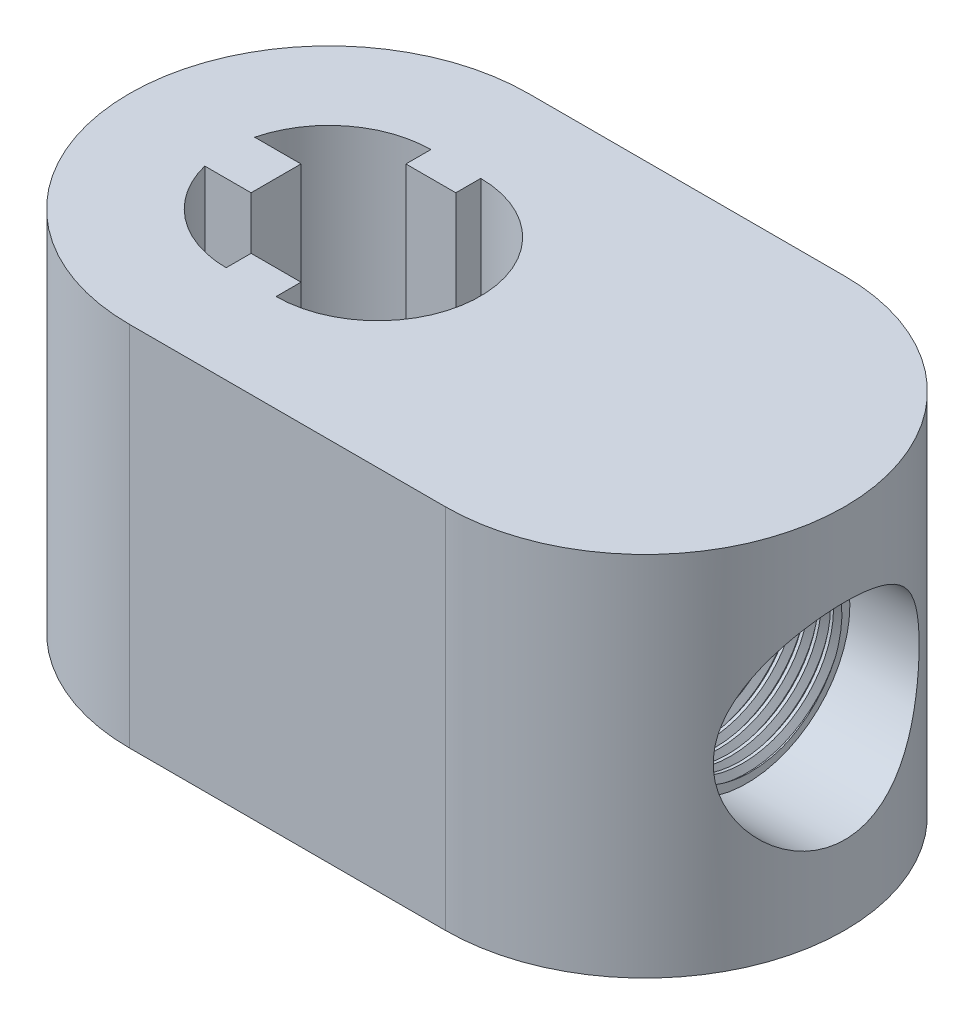
SolidWorks part; units mm, degrees
ref_plane "Front Plane" through (0, 0, 0) normal (0, 0, 1) x (1, 0, 0)
ref_plane "Top Plane" through (0, 0, 0) normal (0, 1, 0) x (1, 0, 0)
ref_plane "Right Plane" through (0, 0, 0) normal (1, 0, 0) x (0, 0, -1)
sketch "Sketch1" plane through (0, 0, 0) normal (0, 1, 0) x (1, 0, 0)
  line L0 (0, 8.165) -> (12.92, 8.165)
  line L1 (0, -8.165) -> (12.92, -8.165)
  circle A0 centre (0, 0) radius 8.165 construction
  arc A1 (12.92, 8.165) -> (12.92, -8.165) centre (12.92, 0) cw
  arc A2 (0, 8.165) -> (0, -8.165) centre (0, 0) ccw
  dimension "D1" = 12.92
  dimension "D2" = 16.33
extrude "Boss-Extrude1" add sketch "Sketch1" along normal blind 15
sketch "Sketch2" plane through (0, 15, 0) normal (0, 1, 0) x (1, 0, 0)
  line L0 (0, 0) -> (2, 0) construction
  line L1 (0, 4.185) -> (2, 4.185)
  line L2 (0, -4.185) -> (2, -4.185)
  arc A1 (0, 4.185) -> (0, -4.185) centre (0, 0) ccw
  arc A2 (2, -4.185) -> (2, 4.185) centre (2, 0) ccw
  point P3 (1, 0)
  dimension "D1" = 8.37
extrude "Cut-Extrude1" cut sketch "Sketch2" against normal blind 11.25
ref_plane "Plane1" through (21.085, 0, 0) normal (1, 0, 0) x (0, 0, -1)
sketch "Sketch3" plane through (21.085, 0, 0) normal (1, 0, 0) x (0, 0, -1)
  line L1 (-8.165, 3.75) -> (8.165, 3.75) construction
  line L2 (-8.165, 15) -> (-8.165, 0) construction
  line L3 (8.165, 15) -> (8.165, 0) construction
  line L4 (8.165, 15) -> (-8.165, 15) construction
  circle A0 centre (0, 7.415) radius 3.665
  dimension "D1" = 7.33
  dimension "D2" = 11.25
extrude "Cut-Extrude2" cut sketch "Sketch3" against normal blind 22
sketch "Sketch4" plane through (21.085, 0, 0) normal (1, 0, 0) x (0, 0, -1)
  circle A0 centre (0, 7.415) radius 4.21
  circle A1 centre (0, 7.415) radius 3.665 construction
  dimension "D1" = 8.42
extrude "Cut-Extrude3" cut sketch "Sketch4" against normal blind 4
thread "Thread1" pitch 0.5 method cut profile "Thread Profile1" start angle 0, offset 4, length 10, pitch 0.5, diameter 7.33
ref_plane "Plane2" through (21.085, 7.415, 3.665) normal (0, -1, 0) x (0, 0, 1)
sketch "Thread Profile1" plane through (21.085, 7.415, 3.665) normal (0, -1, 0) x (0, 0, 1)
  line L0 (0, 0) -> (0, 0.5) construction
  line L1 (0, 0) -> (0.2706, 0.1562)
  line L2 (0.2706, 0.1562) -> (0.2706, 0.2187)
  line L3 (0.2706, 0.2187) -> (0, 0.375)
  line L4 (0.2706, 0.1875) -> (0, 0.1875) construction
  line L11 (0, 0) -> (0, 0.375)
  point P2 (0, 0)
  dimension "Pitch" = 0.5
  dimension "Profile_Angle" = 60
  dimension "Profile_Land" = 0.0625
  dimension "Profile_Height" = 0.2706
sketch "Sketch7" plane through (0, 15, 0) normal (0, 1, 0) x (1, 0, 0)
  line L0 (2, 4.185) -> (0, 4.185) construction
  line L1 (-4.185, 1.02) -> (-2.165, 1.02)
  line L2 (-4.185, 1.02) -> (-4.185, -1.02)
  line L3 (-4.185, -1.02) -> (-2.165, -1.02)
  line L4 (-2.165, 1.02) -> (-2.165, -1.02)
  line L5 (-4.185, 1.02) -> (-2.165, -1.02) construction
  line L6 (-4.185, -1.02) -> (-2.165, 1.02) construction
  line L7 (-0.02, 5.205) -> (2.02, 5.205)
  line L8 (-0.02, 5.205) -> (-0.02, 3.165)
  line L9 (-0.02, 3.165) -> (2.02, 3.165)
  line L10 (2.02, 5.205) -> (2.02, 3.165)
  line L11 (-0.02, 5.205) -> (2.02, 3.165) construction
  line L12 (-0.02, 3.165) -> (2.02, 5.205) construction
  line L13 (-0.02, -3.165) -> (2.02, -3.165)
  line L14 (-0.02, -3.165) -> (-0.02, -5.205)
  line L15 (-0.02, -5.205) -> (2.02, -5.205)
  line L16 (2.02, -3.165) -> (2.02, -5.205)
  line L17 (-0.02, -3.165) -> (2.02, -5.205) construction
  line L18 (-0.02, -5.205) -> (2.02, -3.165) construction
  line L19 (0, -4.185) -> (2, -4.185) construction
  arc A0 (0, 4.185) -> (0, -4.185) centre (0, 0) ccw construction
  point P0 (-3.175, 0)
  point P5 (1, 4.185)
  point P10 (1, -4.185)
  dimension "D1" = 2.04
  dimension "D2" = 2.02
  dimension "D3" = 2.04
  dimension "D4" = 2.04
  dimension "D5" = 2.04
  dimension "D6" = 2.04
extrude "Boss-Extrude2" add sketch "Sketch7" against normal up to surface (11.25 mm away) up to face at (1.5467, 3.75, 0)
sketch "Sketch8" plane through (0, 3.75, 0) normal (0, 1, 0) x (1, 0, 0)
  line L0 (0, 0) -> (2, 0) construction
  line L1 (0, 1.36) -> (2, 1.36)
  line L2 (0, -1.36) -> (2, -1.36)
  arc A0 (0, 1.36) -> (0, -1.36) centre (0, 0) ccw
  arc A1 (2, -1.36) -> (2, 1.36) centre (2, 0) ccw
  arc A2 (2.02, -4.185) -> (6.185, 0) centre (2, 0) ccw construction
  point P3 (1, 0)
  dimension "D1" = 2.72
extrude "Cut-Extrude4" cut sketch "Sketch8" against normal up to surface (3.75 mm away) up to face at (6.46, 0, 0)
sketch "Sketch9" plane through (0, 0, 0) normal (0, -1, 0) x (1, 0, 0)
  line L0 (0, 0) -> (2, 0) construction
  line L1 (0, 2.18) -> (2, 2.18)
  line L2 (0, -2.18) -> (2, -2.18)
  arc A0 (0, 2.18) -> (0, -2.18) centre (0, 0) ccw
  arc A1 (2, -2.18) -> (2, 2.18) centre (2, 0) ccw
  point P3 (1, 0)
  dimension "D2" = 4.36
extrude "Cut-Extrude5" cut sketch "Sketch9" against normal blind 2
equation "\"latch_length\"=12.92"
equation "\"latch_width\"=16.33"
equation "\"latch_thickness\"=15.00"
equation "\"spring_cavity_diameter\"=7.33"
equation "\"latch_keys_width\"=2.04"
equation "\"latch_keys_with_hump\"=2.02"
equation "\"D1@Sketch1\"=\"latch_length\""
equation "\"D2@Sketch1\"=\"latch_width\""
equation "\"D1@Boss-Extrude1\"=\"latch_thickness\""
equation "\"bore_diameter\"=8.37"
equation "\"D1@Sketch2\"=\"bore_diameter\""
equation "\"D1@Sketch3\"=\"spring_cavity_diameter\""
equation "\"bore_depth\"=11.25"
equation "\"D1@Cut-Extrude1\"=\"bore_depth\""
equation "\"D2@Sketch3\"=\"bore_depth\""
equation "\"D1@Sketch7\"=\"latch_keys_width\""
equation "\"D2@Sketch7\"=\"latch_keys_with_hump\""
equation "\"D3@Sketch7\"=\"latch_keys_width\""
equation "\"D4@Sketch7\"=\"latch_keys_width\""
equation "\"D5@Sketch7\"=\"latch_keys_width\""
equation "\"D6@Sketch7\"=\"latch_keys_width\""
equation "\"screw_diameter\"=2.72"
equation "\"D1@Sketch8\"=\"screw_diameter\""
equation "\"spring_screw_countersink_diameter\"=8.42"
equation "\"D1@Sketch4\"=\"spring_screw_countersink_diameter\""
equation "\"screw_countersink_diameter\"=4.36"
equation "\"D2@Sketch9\"=\"screw_countersink_diameter\""
